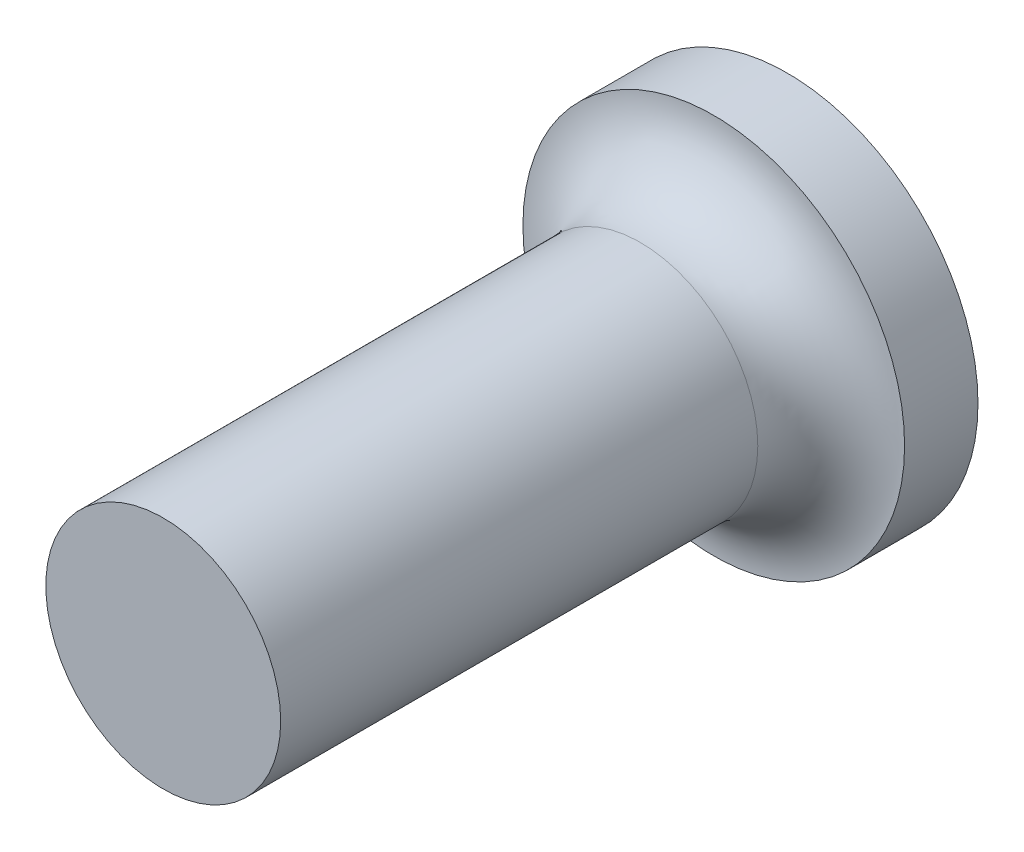
SolidWorks part; units mm, degrees
ref_plane "Спереди" through (0, 0, 0) normal (0, 0, 1) x (1, 0, 0)
ref_plane "Сверху" through (0, 0, 0) normal (0, 1, 0) x (1, 0, 0)
ref_plane "Справа" through (0, 0, 0) normal (1, 0, 0) x (0, 0, -1)
other "Configuration Table"
sketch "Эскиз1" plane through (0, 0, 0) normal (0, 0, 1) x (1, 0, 0)
  circle A0 centre (0, 0) radius 1.6
  dimension "D1" = 3.2
extrude "Бобышка-Вытянуть1" add sketch "Эскиз1" along normal blind 8.5
sketch "Эскиз2" plane through (0, 0, 0) normal (0, 0, 1) x (1, 0, 0)
  circle A0 centre (0, 0) radius 2.6
  dimension "D1" = 5.2
extrude "Бобышка-Вытянуть2" add sketch "Эскиз2" along normal blind 1
fillet "Скругление1" radius 1 1 edges at (1.6, 0, 1)
